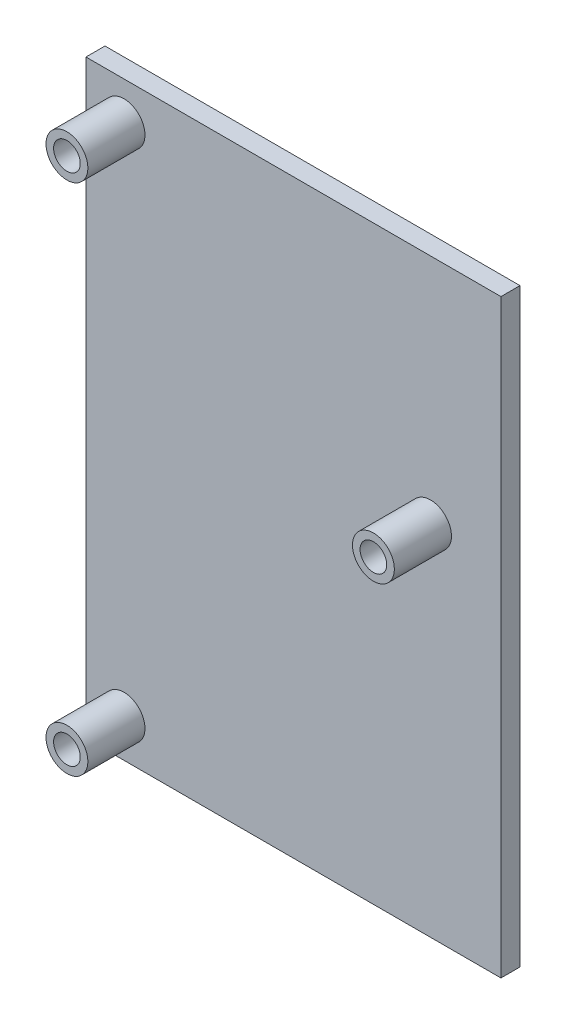
SolidWorks part; units mm, degrees
ref_plane "Front Plane" through (0, 0, 0) normal (1, 0, 0) x (0, 1, 0)
ref_plane "Top Plane" through (0, 0, 0) normal (0, 0, 1) x (0, 1, 0)
ref_plane "Right Plane" through (0, 0, 0) normal (0, 1, 0) x (-1, 0, 0)
sketch "Sketch1" plane through (0, 0, 0) normal (0, 0, 1) x (0, 1, 0)
  line L1 (-38.75, 27.25) -> (38.75, 27.25)
  line L2 (-38.75, 27.25) -> (-38.75, -27.25)
  line L3 (-38.75, -27.25) -> (38.75, -27.25)
  line L4 (38.75, 27.25) -> (38.75, -27.25)
  line L5 (-38.75, 27.25) -> (38.75, -27.25) construction
  line L6 (-38.75, -27.25) -> (38.75, 27.25) construction
  circle A0 centre (-33.75, 22.25) radius 2.75
  circle A1 centre (-33.75, 22.25) radius 1.75
  circle A2 centre (33.75, 22.25) radius 2.75
  circle A3 centre (33.75, 22.25) radius 1.75
  circle A4 centre (8.25, -18) radius 2.75
  circle A5 centre (8.25, -18) radius 1.75
  point P0 (0, 0)
  dimension "D5" = 5.5
  dimension "D6" = 3.5
  dimension "D7" = 5
  dimension "D9" = 5.5
  dimension "D10" = 3.5
  dimension "D13" = 3.5
  dimension "D14" = 5.5
  dimension "D1" = 77.5
  dimension "D2" = 54.5
  dimension "D3" = 5
  dimension "D4" = 5
  dimension "D8" = 5
  dimension "D11" = 47
  dimension "D12" = 45.25
extrude "Boss-Extrude1" add sketch "Sketch1" against normal blind 2.5 contours L1 L4 L3 L2
extrude "Boss-Extrude2" add sketch "Sketch1<5>" along normal blind 7.5 contours A0 A1 | A4 A5 | A2 A3 region at (-22.25, -36.4222, 0) region at (-22.25, 31.0778, 0) region at (18, 5.5778, 0)
sketch "Sketch1<5>" plane through (0, 0, 0) normal (0, 0, 1) x (0, 1, 0) same geometry as "Sketch1"
